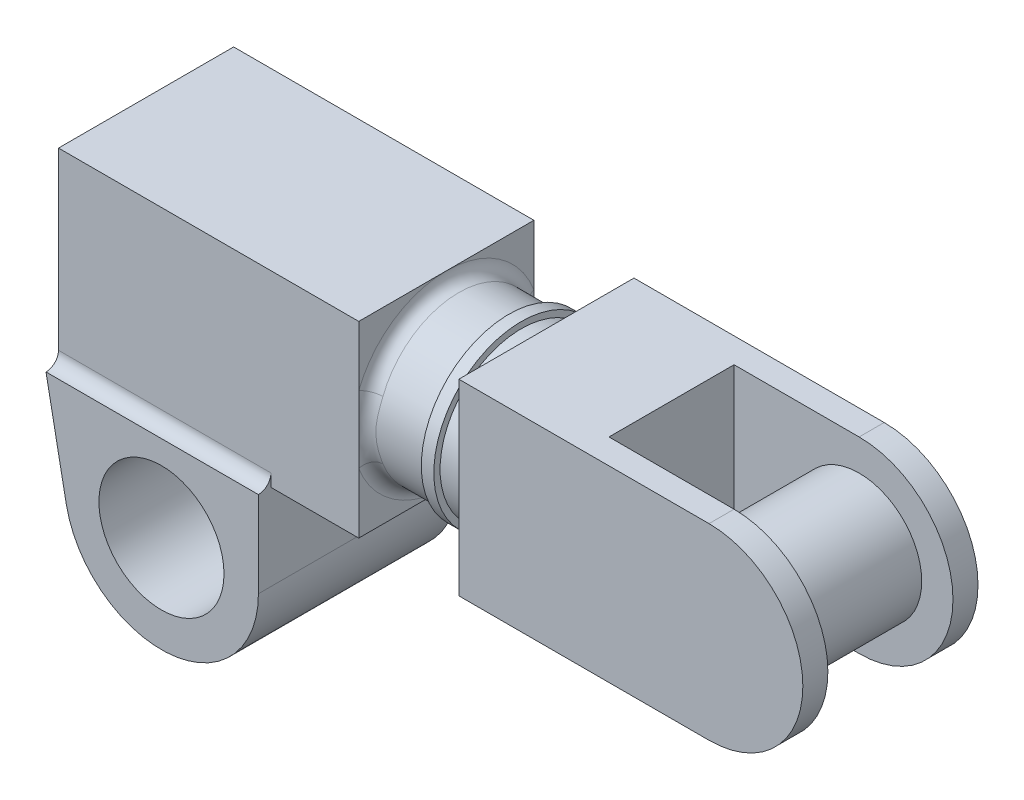
SolidWorks part; units mm, degrees
ref_plane "Front Plane" through (0, 0, 0) normal (0, 0, 1) x (1, 0, 0)
ref_plane "Top Plane" through (0, 0, 0) normal (0, 1, 0) x (1, 0, 0)
ref_plane "Right Plane" through (0, 0, 0) normal (1, 0, 0) x (0, 0, -1)
sketch "Sketch1" plane through (0, 0, 0) normal (1, 0, 0) x (0, 0, -1)
  line L1 (-70, -75) -> (70, -75)
  line L2 (-70, -75) -> (-70, 75)
  line L3 (-70, 75) -> (70, 75)
  line L4 (70, -75) -> (70, 75)
  line L5 (-70, -75) -> (70, 75) construction
  line L6 (-70, 75) -> (70, -75) construction
  point P0 (0, 0)
  dimension "D1" = 140
  dimension "D2" = 150
extrude "Boss-Extrude1" add sketch "Sketch1" along normal blind 240
sketch "Sketch2" plane through (240, 0, 0) normal (1, 0, 0) x (0, 0, -1)
  circle A0 centre (0, 0) radius 65
  dimension "D1" = 130
extrude "Boss-Extrude2" add sketch "Sketch2" along normal blind 50
sketch "Sketch3" plane through (290, 0, 0) normal (1, 0, 0) x (0, 0, -1)
  circle A0 centre (0, 0) radius 70
  dimension "D1" = 140
extrude "Boss-Extrude3" add sketch "Sketch3" along normal blind 10
sketch "Sketch4" plane through (0, 0, 0) normal (0, 0, 1) x (1, 0, 0)
  line L0 (0, -75) -> (16.2188, -158.4383)
  line L1 (0, 75) -> (0, -75) construction
  line L2 (169.7949, -143.6506) -> (169.7949, -75)
  line L3 (240, -75) -> (0, -75) construction
  line L4 (0, -75) -> (169.7949, -75)
  arc A0 (16.2188, -158.4383) -> (169.7949, -143.6506) centre (92.2949, -143.6506) ccw
  circle A1 centre (92.2949, -143.6506) radius 50
  dimension "D1" = 155
  dimension "D2" = 100
  dimension "D3" = 191
  dimension "D4" = 85
extrude "Boss-Extrude4" add sketch "Sketch4" along normal mid plane 160
fillet "Fillet1" radius 10 3 edges at (84.8974, -75, -70) (240, 0, -65) (84.8974, -75, 70)
sketch "Sketch5" plane through (300, 0, 0) normal (1, 0, 0) x (0, 0, -1)
  circle A0 centre (0, 0) radius 65
  dimension "D1" = 130
extrude "Boss-Extrude5" add sketch "Sketch5" along normal blind 20
sketch "Sketch6" plane through (0, 0, 0) normal (0, 0, 1) x (1, 0, 0)
  line L0 (520, 75) -> (320, 75)
  line L1 (320, 75) -> (320, -75)
  line L2 (320, -75) -> (520, -75)
  line L3 (320, -65) -> (320, 65) construction
  arc A0 (520, -75) -> (520, 75) centre (520, 0) ccw
  dimension "D1" = 150
  dimension "D2" = 200
extrude "Boss-Extrude6" add sketch "Sketch6" along normal mid plane 140
sketch "Sketch7" plane through (0, 0, 0) normal (0, 0, 1) x (1, 0, 0)
  line L0 (520, 75) -> (420, 75)
  line L1 (520, 75) -> (320, 75) construction
  line L2 (420, 75) -> (420, -75)
  line L3 (320, -75) -> (520, -75) construction
  line L4 (420, -75) -> (520, -75)
  arc A0 (520, -75) -> (520, 75) centre (520, 0) ccw construction
  arc A1 (520, -75) -> (520, 75) centre (520, 0) ccw
  dimension "D1" = 100
extrude "Cut-Extrude1" cut sketch "Sketch7" against normal mid plane 100
sketch "Sketch8" plane through (0, 0, -50) normal (0, 0, 1) x (1, 0, 0)
  circle A0 centre (520, 0) radius 50
  dimension "D1" = 100
extrude "Boss-Extrude7" add sketch "Sketch8" along normal up to next
